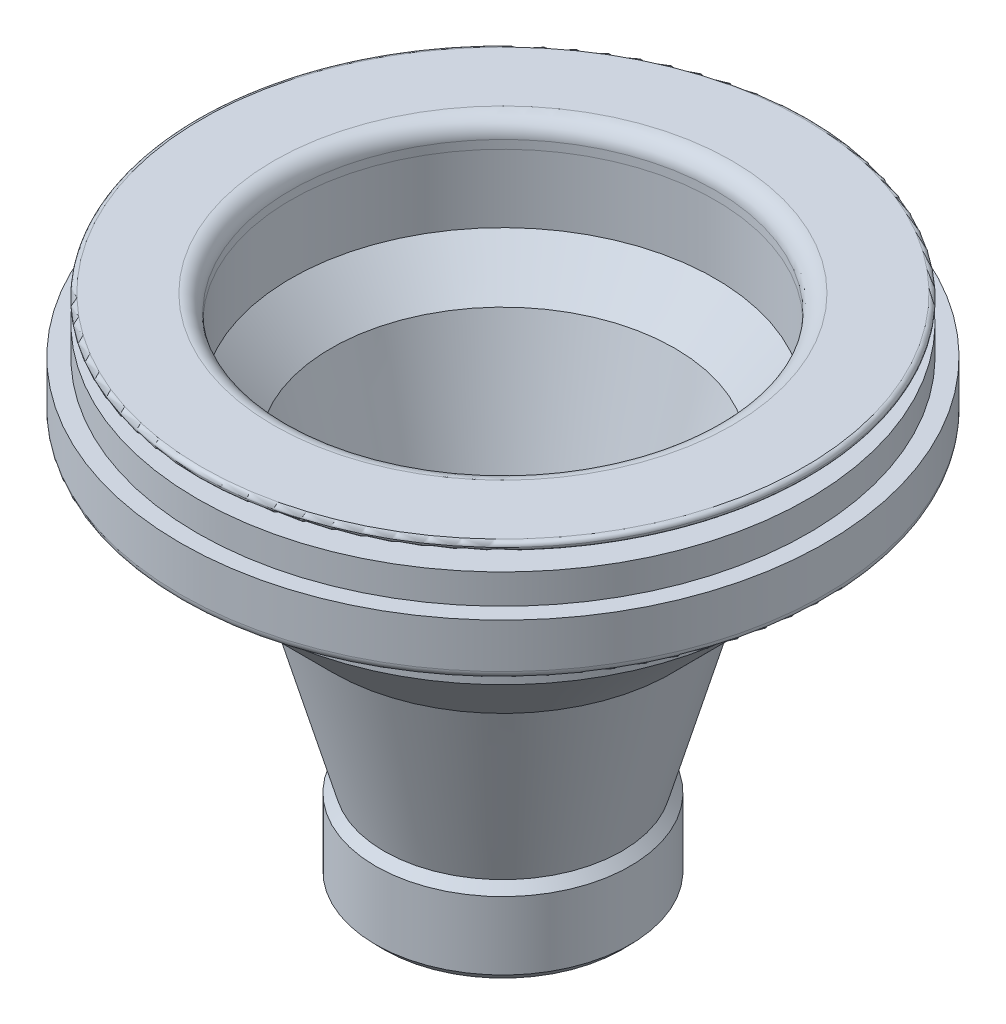
SolidWorks part; units mm, degrees
material "Chrome Stainless Steel"
ref_plane "Front Plane" through (0, 0, 0) normal (0, 0, 1) x (1, 0, 0)
ref_plane "Top Plane" through (0, 0, 0) normal (0, 1, 0) x (1, 0, 0)
ref_plane "Right Plane" through (0, 0, 0) normal (1, 0, 0) x (0, 0, -1)
ref_plane "SinkDrainTopPlane" through (0, -228.6, 0) normal (0, 1, 0) x (1, 0, 0)
sketch "DrainPosSketch" plane through (0, -228.6, 0) normal (0, 1, 0) x (1, 0, 0)
  line L0 (419.1, 444.5) -> (419.1, 38.1) construction
  line L1 (0, 0) -> (838.2, 0) construction
  line L2 (0, 0) -> (0, 558.8) construction
  line L3 (0, 558.8) -> (838.2, 558.8) construction
  line L4 (838.2, 0) -> (838.2, 558.8) construction
  line L5 (25.4, 38.1) -> (812.8, 38.1) construction
  line L6 (25.4, 38.1) -> (25.4, 444.5) construction
  line L7 (25.4, 444.5) -> (812.8, 444.5) construction
  line L8 (812.8, 38.1) -> (812.8, 444.5) construction
  line L13 (25.4, 241.3) -> (812.8, 241.3) construction
  circle A0 centre (685.8, 317.5) radius 44.45 construction
  circle A5 centre (685.8, 317.5) radius 57.15
  dimension "D7" = 88.9
  dimension "D13" = 114.3
  dimension "D1" = 838.2
  dimension "D2" = 558.8
  dimension "D3" = 406.4
  dimension "D4" = 787.4
  dimension "D5" = 25.4
  dimension "D6" = 114.3
  dimension "D8" = 127
  dimension "D9" = 127
ref_plane "DrainProfilePlanePlane" through (0, 0, -317.5) normal (0, 0, 1) x (1, 0, 0)
sketch "DrainSketch" plane through (0, 0, -317.5) normal (0, 0, 1) x (1, 0, 0)
  line L0 (685.8, -228.6) -> (685.8, -322.2625)
  line L1 (742.95, -228.6) -> (628.65, -228.6) construction
  line L2 (628.65, -228.6) -> (742.95, -228.6)
  line L3 (25.4, -228.6) -> (812.8, -228.6) construction
  line L4 (730.25, -228.6) -> (730.25, -231.775)
  line L5 (730.25, -231.775) -> (685.8, -231.775)
  line L6 (742.95, -228.6) -> (742.95, -227.0125)
  line L7 (742.95, -227.0125) -> (725.4875, -227.0125)
  line L8 (725.4875, -227.0125) -> (725.4875, -231.775)
  line L9 (730.25, -231.775) -> (742.95, -231.775)
  line L10 (742.95, -231.775) -> (742.95, -237.3313)
  line L11 (685.8, -237.3313) -> (746.125, -237.3313)
  line L12 (746.125, -237.3313) -> (746.125, -245.2688)
  line L13 (746.125, -245.2688) -> (685.8, -245.2688)
  line L14 (685.8, -247.2531) -> (744.5375, -247.2531)
  line L15 (746.125, -245.6656) -> (746.125, -245.2688)
  line L16 (733.425, -247.2531) -> (733.425, -256.7781)
  line L17 (733.425, -256.7781) -> (685.8, -256.7781)
  line L18 (733.425, -256.7781) -> (717.55, -272.6531)
  line L19 (717.55, -272.6531) -> (685.8, -272.6531)
  line L20 (685.8, -306.3081) -> (708.025, -306.3081)
  line L21 (708.025, -306.3081) -> (717.55, -272.6531)
  line L22 (685.8, -322.2625) -> (708.025, -322.2625)
  line L23 (708.025, -322.2625) -> (708.025, -306.3081) construction
  line L24 (708.025, -306.3081) -> (709.6125, -307.9353)
  line L25 (709.6125, -307.9353) -> (709.6125, -320.6353)
  line L26 (709.6125, -320.6353) -> (708.025, -322.2625)
  line L27 (709.6125, -314.2853) -> (708.025, -314.2853) construction
  line L29 (704.85, -298.2913) -> (704.85, -322.2625)
  line L30 (725.4875, -231.775) -> (725.4875, -244.475)
  line L31 (725.4875, -244.475) -> (717.9469, -252.0156)
  line L32 (717.9469, -252.0156) -> (704.85, -298.2913)
  arc A0 (744.5375, -247.2531) -> (746.125, -245.6656) centre (744.5375, -245.6656) ccw
  point P42 (733.425, -252.0156)
  dimension "D10" = 1.5875
  dimension "D1" = 1.5875
  dimension "D2" = 114.3
  dimension "D3" = 3.175
  dimension "D4" = 44.45
  dimension "D5" = 95.25
  dimension "D6" = 39.6875
  dimension "D7" = 5.5562
  dimension "D8" = 7.9375
  dimension "D9" = 1.9844
  dimension "D11" = 60.325
  dimension "D12" = 9.525
  dimension "D13" = 47.625
  dimension "D14" = 31.75
  dimension "D15" = 15.875
  dimension "D16" = 22.225
  dimension "D17" = 33.655
  dimension "D18" = 12.7
  dimension "D19" = 1.5875
  dimension "D20" = 19.05
  dimension "D21" = 12.7
revolve "DrainUnderRevolve" add sketch "DrainSketch" angle 360 about L0 region at (734.2187, -234.5531, -317.5) region at (735.7859, -241.3071, -317.5) region at (734.7723, -246.2679, -317.5) region at (725.9981, -252.3473, -317.5) region at (720.7875, -263.3633, -317.5) region at (710.3775, -288.7413, -317.5) region at (707.1661, -314.2853, -317.5)
revolve "DrainPlateRevolve" add sketch "DrainSketch<3>" angle 360 about L0 region at (734.2188, -227.8063, -317.5) region at (727.8687, -230.1875, -317.5)
sketch "DrainSketch<3>" plane through (0, 0, -317.5) normal (0, 0, 1) x (1, 0, 0) same geometry as "DrainSketch"
fillet "DrainInFillet" radius 3.175 1 edges at (685.8, -227.0125, -277.8125)
fillet "RimFillet" radius 0.7937 2 edges at (685.8, -228.6, -260.35) (685.8, -227.0125, -260.35)
